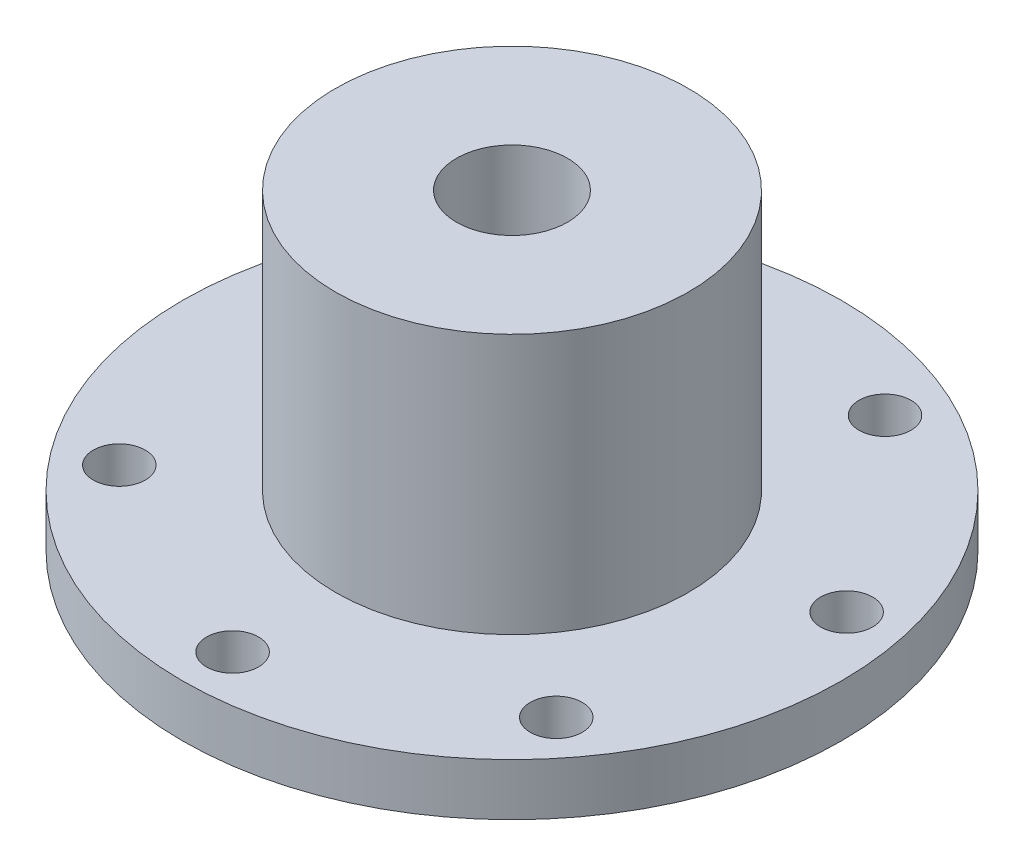
SolidWorks part; units mm, degrees
ref_plane "Front Plane" through (0, 0, 0) normal (0, 0, 1) x (1, 0, 0)
ref_plane "Top Plane" through (0, 0, 0) normal (0, 1, 0) x (1, 0, 0)
ref_plane "Right Plane" through (0, 0, 0) normal (1, 0, 0) x (0, 0, -1)
sketch "Sketch1" plane through (0, 0, 0) normal (0, 1, 0) x (1, 0, 0)
  circle A0 centre (0, 0) radius 3.2
  circle A1 centre (0, 0) radius 10.175
  circle A2 centre (0, 0) radius 19
  point P25 (0, 0)
extrude "Boss-Extrude1" add sketch "Sketch1" along normal blind 15 and the other way blind 3 contours A1 A0 region at (-9.8872, 0, 0)
extrude "Boss-Extrude2" add sketch "Sketch1<3>" against normal blind 3 separate body contours A2 A1 region at (-18.4626, 0, 0)
sketch "Sketch1<3>" plane through (0, 0, 0) normal (0, 1, 0) x (1, 0, 0) same geometry as "Sketch1"
sketch "Sketch2" plane through (0, 0, 0) normal (1, 0, 0) x (0, 0, -1)
  circle A0 centre (0, 6.7029) radius 1.25
extrude "Cut-Extrude1" cut sketch "Sketch2" against normal blind 15
sketch "Sketch3" plane through (0, -3, 0) normal (0, -1, 0) x (1, 0, 0)
  circle A0 centre (0, 16.1125) radius 1.5
  circle A2 centre (12.5973, 10.046) radius 1.5
  circle A3 centre (15.7086, -3.5854) radius 1.5
  circle A4 centre (6.991, -14.5169) radius 1.5
  circle A5 centre (-6.991, -14.5169) radius 1.5
  circle A6 centre (-15.7086, -3.5854) radius 1.5
  circle A7 centre (-12.5973, 10.046) radius 1.5
  point P14 (0, 0)
  point P16 (0, 0)
  point P17 (0, 16.1125)
  dimension "D1" = 7
sketch "Sketch4" plane through (0, -3, 0) normal (0, -1, 0) x (1, 0, 0)
  circle A0 centre (0, 0) radius 4.5
extrude "Boss-Extrude3" add sketch "Sketch4" along normal blind 10 contours A0
extrude "Cut-Extrude2" cut sketch "Sketch1<7>" against normal blind 13 contours A0
sketch "Sketch1<7>" plane through (0, 0, 0) normal (0, 1, 0) x (1, 0, 0) same geometry as "Sketch1"
extrude "Cut-Extrude3" cut sketch "Sketch3" against normal blind 10
